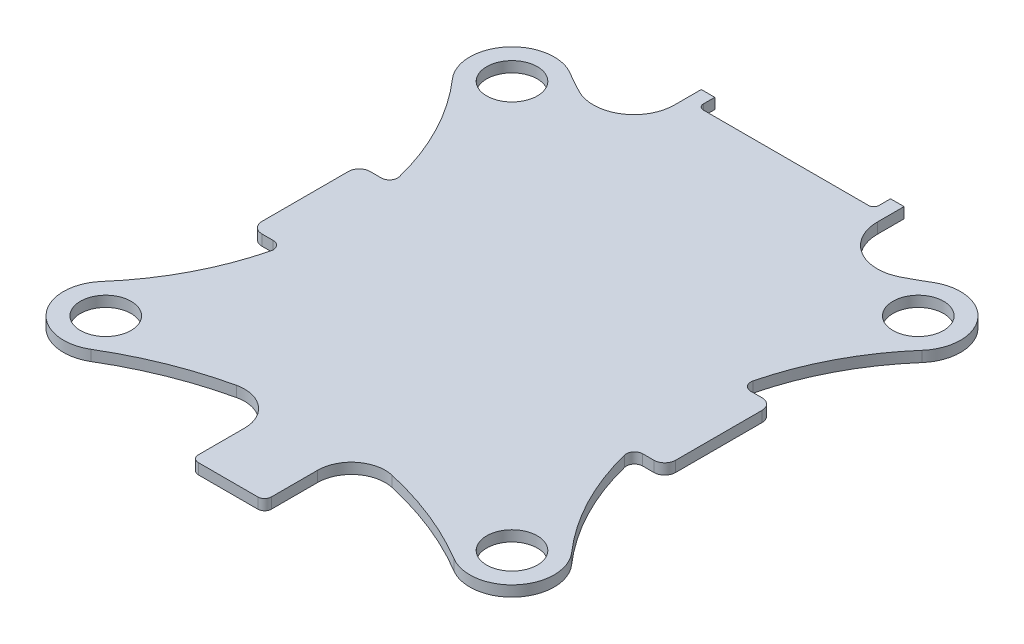
SolidWorks part; units mm, degrees
ref_plane "Front Plane" through (0, 0, 0) normal (0, 0, 1) x (1, 0, 0)
ref_plane "Top Plane" through (0, 0, 0) normal (0, 1, 0) x (1, 0, 0)
ref_plane "Right Plane" through (0, 0, 0) normal (1, 0, 0) x (0, 0, -1)
sketch "Sketch1" plane through (0, 0, 0) normal (0, 1, 0) x (1, 0, 0)
  line L0 (-19.083, 19.083) -> (19.083, -19.083) construction
  line L1 (-15.875, -17.78) -> (15.875, -17.78) construction
  line L2 (-15.875, -17.78) -> (-15.875, 17.78) construction
  line L3 (-15.875, 17.78) -> (15.875, 17.78) construction
  line L4 (15.875, -17.78) -> (15.875, 17.78) construction
  line L5 (-19.083, -19.083) -> (19.083, 19.083) construction
  line L6 (-21.8894, -16.2767) -> (-16.2767, -21.8894) construction
  line L7 (0, -17.78) -> (0, 17.78) construction
  line L8 (-15.875, 0) -> (15.875, 0) construction
  line L9 (21.8894, -16.2767) -> (16.2767, -21.8894) construction
  line L10 (-21.8894, 16.2767) -> (-16.2767, 21.8894) construction
  line L11 (21.8894, 16.2767) -> (16.2767, 21.8894) construction
  line L12 (-17.3519, -5.08) -> (-18.415, -5.08)
  line L13 (-19.431, -4.064) -> (-19.431, 4.064)
  line L14 (-18.415, 5.08) -> (-17.3519, 5.08)
  line L15 (18.415, 5.08) -> (17.3519, 5.08)
  line L16 (19.431, -4.064) -> (19.431, 4.064)
  line L17 (-3.429, -21.6901) -> (-3.429, -26.035)
  line L18 (-2.794, -26.67) -> (2.794, -26.67)
  line L19 (3.429, -26.035) -> (3.429, -21.6901)
  line L20 (-9.525, 24.7886) -> (-9.525, 27.305)
  line L21 (-9.525, 27.305) -> (9.525, 27.305) construction
  line L22 (9.525, 27.305) -> (9.525, 24.7886)
  line L23 (-8.255, 27.305) -> (-8.255, 26.2382)
  line L24 (-7.747, 25.7302) -> (7.747, 25.7302)
  line L25 (8.255, 26.2382) -> (8.255, 27.305)
  line L26 (8.255, 27.305) -> (9.525, 27.305)
  line L27 (-8.255, 27.305) -> (-9.525, 27.305)
  line L28 (17.3519, -5.08) -> (18.415, -5.08)
  circle A0 centre (-19.083, -19.083) radius 3.9688 construction
  circle A1 centre (19.083, -19.083) radius 3.9688 construction
  circle A2 centre (19.083, 19.083) radius 3.9688 construction
  circle A3 centre (-19.083, 19.083) radius 3.9688 construction
  arc A4 (-22.0682, 16.4678) -> (-22.0682, -16.4678) centre (-40.8655, 0) cw construction
  arc A5 (-17.0457, 22.489) -> (17.0457, 22.489) centre (0, 50.9859) ccw construction
  arc A6 (-17.0457, -22.489) -> (17.0457, -22.489) centre (0, -50.9859) cw construction
  arc A7 (22.0682, 16.4678) -> (22.0682, -16.4678) centre (40.8655, 0) ccw construction
  arc A8 (-22.0682, 16.4678) -> (-17.0457, 22.489) centre (-19.083, 19.083) cw
  arc A9 (17.0457, 22.489) -> (22.0682, 16.4678) centre (19.083, 19.083) cw
  arc A10 (22.0682, -16.4678) -> (17.0457, -22.489) centre (19.083, -19.083) cw
  arc A11 (-22.0682, -16.4678) -> (-17.0457, -22.489) centre (-19.083, -19.083) ccw
  circle A12 centre (-19.083, -19.083) radius 2.3813
  circle A13 centre (19.083, -19.083) radius 2.3813
  circle A14 centre (19.083, 19.083) radius 2.3813
  circle A15 centre (-19.083, 19.083) radius 2.3813
  arc A16 (-22.0682, -16.4678) -> (-16.6123, -6.0257) centre (-40.8655, 0) ccw
  arc A17 (-17.3519, -5.08) -> (-16.6123, -6.0257) centre (-17.3519, -5.842) cw
  arc A18 (-22.0682, 16.4678) -> (-16.6123, 6.0257) centre (-40.8655, 0) cw
  arc A19 (-16.6123, 6.0257) -> (-17.3519, 5.08) centre (-17.3519, 5.842) cw
  arc A20 (-18.415, 5.08) -> (-19.431, 4.064) centre (-18.415, 4.064) ccw
  arc A21 (-19.431, -4.064) -> (-18.415, -5.08) centre (-18.415, -4.064) ccw
  arc A22 (16.6123, 6.0257) -> (17.3519, 5.08) centre (17.3519, 5.842) ccw
  arc A23 (22.0682, 16.4678) -> (16.6123, 6.0257) centre (40.8655, 0) ccw
  arc A24 (22.0682, -16.4678) -> (16.6123, -6.0257) centre (40.8655, 0) cw
  arc A25 (17.3519, -5.08) -> (16.6123, -6.0257) centre (17.3519, -5.842) ccw
  arc A26 (19.431, -4.064) -> (18.415, -5.08) centre (18.415, -4.064) cw
  arc A27 (18.415, 5.08) -> (19.431, 4.064) centre (18.415, 4.064) cw
  arc A28 (-17.0457, -22.489) -> (-7.3022, -18.5929) centre (0, -50.9859) cw
  arc A29 (17.0457, -22.489) -> (7.3022, -18.5929) centre (0, -50.9859) ccw
  arc A30 (-7.3022, -18.5929) -> (-3.429, -21.6901) centre (-6.604, -21.6901) cw
  arc A31 (7.3022, -18.5929) -> (3.429, -21.6901) centre (6.604, -21.6901) ccw
  arc A32 (-3.429, -26.035) -> (-2.794, -26.67) centre (-2.794, -26.035) ccw
  arc A33 (3.429, -26.035) -> (2.794, -26.67) centre (2.794, -26.035) cw
  arc A34 (-17.0457, 22.489) -> (-15.0633, 21.3932) centre (0, 50.9859) ccw
  arc A35 (17.0457, 22.489) -> (15.0633, 21.3932) centre (0, 50.9859) cw
  arc A36 (-9.525, 24.7886) -> (-15.0633, 21.3932) centre (-13.335, 24.7886) cw
  arc A37 (9.525, 24.7886) -> (15.0633, 21.3932) centre (13.335, 24.7886) ccw
  arc A38 (-8.255, 26.2382) -> (-7.747, 25.7302) centre (-7.747, 26.2382) ccw
  arc A39 (8.255, 26.2382) -> (7.747, 25.7302) centre (7.747, 26.2382) cw
  point P4 (0, 17.78)
  point P6 (15.875, 0)
  point P11 (0, 0)
  point P12 (0, 0)
  point P19 (-19.083, -19.083)
  point P60 (-19.431, 5.08)
  point P63 (-19.431, -5.08)
  point P72 (19.431, -5.08)
  point P73 (19.431, 5.08)
  point P82 (3.429, -17.9575)
  point P85 (-3.429, -26.67)
  point P88 (3.429, -26.67)
  point P95 (-9.525, 19.1754)
  point P98 (9.525, 19.1754)
  point P103 (0, 25.7302)
  point P104 (0, 27.305)
  dimension "D3" = 7.9375
  dimension "D8" = 0.762
  dimension "D9" = 0.762
  dimension "D10" = 1.016
  dimension "D11" = 1.016
  dimension "D14" = 3.175
  dimension "D15" = 3.175
  dimension "D16" = 0.635
  dimension "D17" = 0.635
  dimension "D20" = 3.81
  dimension "D21" = 3.81
  dimension "D22" = 4.7625
  dimension "D25" = 0.508
  dimension "D26" = 0.508
  dimension "D1" = 31.75
  dimension "D2" = 35.56
  dimension "D4" = 53.975
  dimension "D5" = 3.556
  dimension "D6" = 5.08
  dimension "D7" = 5.08
  dimension "D12" = 6.858
  dimension "D13" = 8.89
  dimension "D18" = 9.525
  dimension "D19" = 19.05
  dimension "D23" = 1.5748
  dimension "D24" = 1.27
extrude "Boss-Extrude2" add sketch "Sketch1" along normal blind 1 contours A12 | A13 | A14 | A15 | A28 A30 L17 A32 L18 A33 L19 A31 A29 A10 A24 A25 L28 A26 L16 A27 L15 A22 A23 A9 A35 A37 L22 L26 L25 A39 L24 A38 L23 L27 L20 A36 A34 A8 A18 A19 L14 A20 L13 A21 L12 A17 A16 A11 region at (-19.083, 0, 19.083) region at (19.083, 0, 19.083) region at (19.083, 0, -19.083) region at (-19.083, 0, -19.083)
